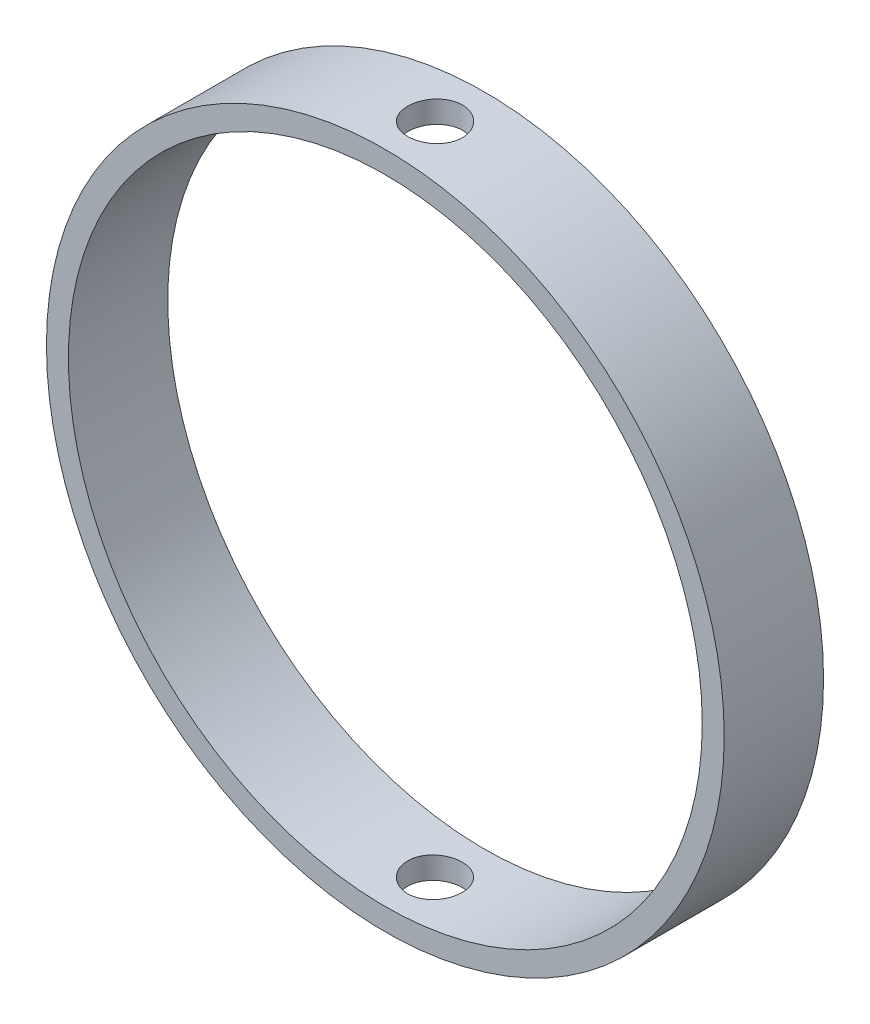
SolidWorks part; units mm, degrees
ref_plane "Front Plane" through (0, 0, 0) normal (0, 0, 1) x (1, 0, 0)
ref_plane "Top Plane" through (0, 0, 0) normal (0, 1, 0) x (1, 0, 0)
ref_plane "Right Plane" through (0, 0, 0) normal (1, 0, 0) x (0, 0, -1)
sketch "Sketch1" plane through (0, 0, 0) normal (0, 0, 1) x (1, 0, 0)
  circle A0 centre (0, 0) radius 34.11
  circle A1 centre (0, 0) radius 31.9
  dimension "D1" = 68.22
  dimension "D2" = 63.8
extrude "Boss-Extrude1" add sketch "Sketch1" along normal blind 10
ref_plane "Plane1" through (0, 34.11, 0) normal (0, 1, 0) x (1, 0, 0)
sketch "Sketch2" plane through (0, 34.11, 0) normal (0, 1, 0) x (1, 0, 0)
  circle A0 centre (0, -5) radius 2.75
  dimension "D1" = 5.5
  dimension "D2" = 5
extrude "Cut-Extrude1" cut sketch "Sketch2" against normal through all
